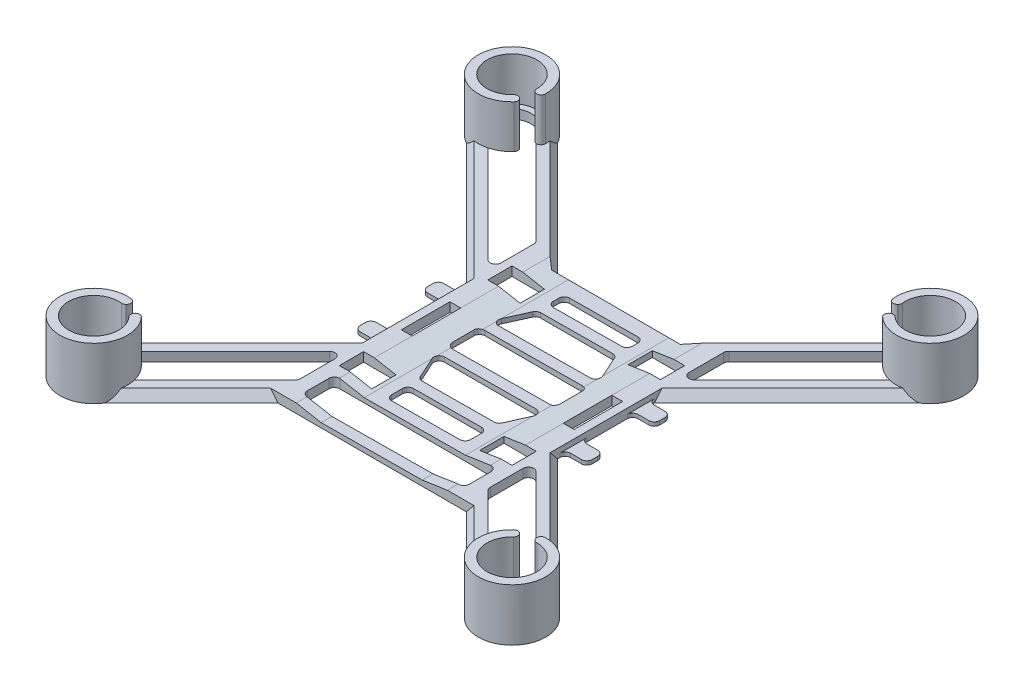
SolidWorks part; units mm, degrees
ref_plane "Plano frontal" through (0, 0, 0) normal (0, 0, 1) x (1, 0, 0)
ref_plane "Plano superior" through (0, 0, 0) normal (0, 1, 0) x (1, 0, 0)
ref_plane "Plano direito" through (0, 0, 0) normal (1, 0, 0) x (0, 0, -1)
sketch "Esboço1" plane through (0, 0, 0) normal (0, 1, 0) x (1, 0, 0)
  line L1 (-45, 45) -> (45, 45)
  line L2 (-45, 45) -> (-45, -45)
  line L3 (-45, -45) -> (45, -45)
  line L4 (45, 45) -> (45, -45)
  line L5 (-45, 45) -> (45, -45) construction
  line L6 (-45, -45) -> (45, 45) construction
  point P0 (0, 0)
  dimension "D1" = 90
  dimension "D2" = 90
extrude "Ressalto-extrusão1" add sketch "Esboço1" along normal blind 1.7
sketch "Esboço2" plane through (0, 1.7, 0) normal (0, 1, 0) x (1, 0, 0)
  line L0 (-45, 45) -> (-45, -45) construction
  line L1 (45, 45) -> (-45, 45) construction
  line L3 (45, -45) -> (45, 45) construction
  line L4 (-45, -45) -> (45, -45) construction
  circle A0 centre (-38.75, 38.75) radius 4.625
  circle A1 centre (38.75, 38.75) radius 4.625
  circle A2 centre (-38.75, -38.75) radius 4.625
  circle A3 centre (38.75, -38.75) radius 4.625
  circle A4 centre (-38.75, 38.75) radius 6.25
  circle A5 centre (38.75, 38.75) radius 6.25
  circle A6 centre (38.75, -38.75) radius 6.25
  circle A7 centre (-38.75, -38.75) radius 6.25
  dimension "D1" = 9.25
  dimension "D2" = 9.25
  dimension "D3" = 9.25
  dimension "D4" = 9.25
  dimension "D5" = 12.5
  dimension "D6" = 12.5
  dimension "D7" = 12.5
  dimension "D8" = 12.5
extrude "Ressalto-extrusão2" add sketch "Esboço2" along normal blind 8
fillet "Filete1" radius 6.25 4 edges at (-45, 0.85, -45) (45, 0.85, -45) (45, 0.85, 45) (-45, 0.85, 45)
sketch "Esboço3" plane through (0, 1.7, 0) normal (0, 1, 0) x (1, 0, 0)
  line L0 (0.3066, 3.9483) -> (37.2235, 40.8652)
  line L1 (40.8775, -36.6225) -> (39.4633, -38.0367)
  line L2 (-40.7706, -37.1289) -> (-39.3564, -38.5431)
  line L3 (-40.7706, -37.1289) -> (-1.1076, 2.5341)
  line L4 (37.2235, 40.8652) -> (38.6377, 39.451)
  line L5 (38.6377, 39.451) -> (1.7208, 2.5341)
  line L7 (40.8775, -36.6225) -> (1.7208, 2.5341)
  line L8 (-36.3856, 40.6405) -> (-37.7998, 39.2263)
  line L9 (-37.7998, 39.2263) -> (-1.1076, 2.5341)
  line L11 (0.3066, 3.9483) -> (-36.3856, 40.6405)
  line L12 (0.3066, 1.1199) -> (-39.3564, -38.5431)
  line L13 (0.3066, 1.1199) -> (39.4633, -38.0367)
  dimension "D1" = 2
  dimension "D3" = 2
extrude "Corte-extrusão1" cut sketch "Esboço3" along normal blind 15
sketch "Esboço11" plane through (0, 1.7, 0) normal (0, 1, 0) x (1, 0, 0)
  line L1 (-16, -16) -> (-10, -16)
  line L2 (-16, -16) -> (-16, -11.5)
  line L3 (-16, -11.5) -> (-10, -11.5)
  line L4 (-10, -16) -> (-10, -11.5)
  line L5 (-16, -4.5) -> (-14, -4.5)
  line L6 (-16, -4.5) -> (-16, 4.5)
  line L7 (-16, 4.5) -> (-14, 4.5)
  line L8 (-14, -4.5) -> (-14, 4.5)
  line L9 (-16, 11.5) -> (-10, 11.5)
  line L10 (-16, 11.5) -> (-16, 16)
  line L11 (-16, 16) -> (-10, 16)
  line L12 (-10, 11.5) -> (-10, 16)
  line L13 (10, -16) -> (16, -16)
  line L14 (10, -16) -> (10, -11.5)
  line L15 (10, -11.5) -> (16, -11.5)
  line L16 (16, -16) -> (16, -11.5)
  line L17 (16, -4.5) -> (14, -4.5)
  line L18 (16, -4.5) -> (16, 4.5)
  line L19 (16, 4.5) -> (14, 4.5)
  line L20 (14, -4.5) -> (14, 4.5)
  line L21 (16, 11.5) -> (10, 11.5)
  line L22 (16, 11.5) -> (16, 16)
  line L23 (16, 16) -> (10, 16)
  line L24 (10, 11.5) -> (10, 16)
  point P24 (-14, 0)
  dimension "D1" = 6
  dimension "D2" = 6
  dimension "D3" = 28
  dimension "D4" = 2
  dimension "D5" = 2
  dimension "D6" = 9
  dimension "D7" = 7
  dimension "D8" = 7
  dimension "D9" = 4.5
  dimension "D10" = 4.5
  dimension "D11" = 14
  dimension "D12" = 14
extrude "Corte-extrusão8" cut sketch "Esboço11" against normal blind 20
sketch "Esboço14" plane through (0, 1.7, 0) normal (0, 1, 0) x (1, 0, 0)
  line L2 (-34.3319, -43.1681) -> (-17.1431, -25.9793)
  line L3 (-44.9981, -38.75) -> (-47.943, -38.75)
  line L4 (-47.943, -38.75) -> (-47.943, 38.75)
  line L5 (-43.1681, -34.3319) -> (-17.5, -8.6638)
  line L6 (-34.3319, -43.1681) -> (-33.4507, -42.0602) construction
  line L7 (43.1681, 34.3319) -> (42.0602, 33.4507) construction
  line L8 (34.4073, -43.0927) -> (17.2939, -25.9793)
  line L9 (-47.943, 38.75) -> (-44.8915, 38.75)
  line L10 (-38.75, 44.8915) -> (-38.75, 46.9757)
  line L11 (43.0927, -34.4073) -> (17.5, -8.8146)
  line L12 (34.4073, -43.0927) -> (33.5537, -42.0237) construction
  line L13 (-43.0927, 34.4073) -> (-42.0237, 33.5537) construction
  line L15 (-38.75, 46.9757) -> (38.75, 46.9757)
  line L16 (-12.3146, 21) -> (12.1638, 21)
  line L17 (17.5, 8.6638) -> (17.5, -8.8146)
  line L18 (38.75, 46.9757) -> (38.75, 44.9981)
  line L22 (-17.5, 8.8146) -> (-43.0927, 34.4073)
  line L23 (17.5, 8.6638) -> (43.1681, 34.3319)
  line L24 (42.0237, -33.5537) -> (43.0927, -34.4073) construction
  line L25 (-33.5537, 42.0237) -> (-34.4073, 43.0927) construction
  line L26 (-12.3146, 21) -> (-34.4073, 43.0927)
  line L27 (12.1638, 21) -> (34.3319, 43.1681)
  line L28 (-17.5, 8.8146) -> (-17.5, -8.6638)
  line L29 (-17.1431, -25.9793) -> (17.2939, -25.9793)
  line L30 (44.9981, 38.75) -> (47.7164, 38.75)
  line L31 (47.7164, 38.75) -> (47.7164, -38.75)
  line L32 (47.7164, -38.75) -> (44.8915, -38.75)
  line L33 (-38.75, -44.9981) -> (-38.75, -47.5867)
  line L34 (-38.75, -47.5867) -> (38.75, -47.5867)
  line L35 (38.75, -47.5867) -> (38.75, -44.8915)
  line L36 (33.4507, 42.0602) -> (34.3319, 43.1681) construction
  line L37 (-42.0602, -33.4507) -> (-43.1681, -34.3319) construction
  arc A0 (-33.5537, 42.0237) -> (-38.75, 44.8915) centre (-38.75, 38.75) ccw
  arc A1 (42.0602, 33.4507) -> (44.9981, 38.75) centre (38.75, 38.75) ccw
  arc A2 (33.5537, -42.0237) -> (38.75, -44.8915) centre (38.75, -38.75) ccw
  arc A3 (-42.0602, -33.4507) -> (-44.9981, -38.75) centre (-38.75, -38.75) ccw
  arc A4 (-38.75, -44.9981) -> (-33.4507, -42.0602) centre (-38.75, -38.75) ccw
  arc A5 (44.8915, -38.75) -> (42.0237, -33.5537) centre (38.75, -38.75) ccw
  arc A6 (-44.8915, 38.75) -> (-42.0237, 33.5537) centre (-38.75, 38.75) ccw
  arc A7 (38.75, 44.9981) -> (33.4507, 42.0602) centre (38.75, 38.75) ccw
  point P8 (0, 0)
  point P9 (0, 0)
  point P10 (0, 0)
  arc M28 (37.0038, -32.7489) -> (45, -38.75) centre (38.75, -38.75) cw
  line M29 (45, -38.75) -> (45, 38.75)
  arc M30 (45, 38.75) -> (33.9427, 34.756) centre (38.75, 38.75) cw
  arc M34 (32.9023, 36.544) -> (38.75, 45) centre (38.75, 38.75) cw
  line M35 (38.75, 45) -> (-38.75, 45)
  arc M36 (-38.75, 45) -> (-32.7489, 37.0038) centre (-38.75, 38.75) cw
  arc M40 (-33.6753, 35.1018) -> (-45, 38.75) centre (-38.75, 38.75) cw
  line M41 (-45, 38.75) -> (-45, -38.75)
  arc M42 (-45, -38.75) -> (-36.544, -32.9023) centre (-38.75, -38.75) cw
  arc M46 (-34.756, -33.9427) -> (-38.75, -45) centre (-38.75, -38.75) cw
  line M47 (-38.75, -45) -> (38.75, -45)
  arc M48 (38.75, -45) -> (35.1018, -33.6753) centre (38.75, -38.75) cw
extrude "Corte-extrusão11" cut sketch "Esboço14" against normal blind 23 contours L28 L22 L5 M40 M41 M42 | L16 L27 L26 M34 M35 M36 | L23 L17 L11 M28 M29 M30 | L29 L2 L8 M46 M47 M48
sketch "Esboço17" plane through (0, 1.7, 0) normal (0, 1, 0) x (1, 0, 0)
  line L0 (17.5, 8.6638) -> (17.5, -8.8146) construction
  line L1 (-12.3146, 21) -> (-33.5874, 42.2728) construction
  line L2 (-40.125, -35.5314) -> (-17.5, -12.9064)
  line L3 (-17.5, 13.0572) -> (-17.5, 21.9428)
  line L4 (-17.5, 8.8146) -> (-17.5, -8.6638) construction
  line L5 (-35.5314, -40.125) -> (-17.5, -22.0936)
  line L7 (17.5, 8.6638) -> (43.0606, 34.2244) construction
  line L8 (-39.8803, 35.4375) -> (-17.5, 13.0572)
  line L9 (-17.5, 8.8146) -> (-42.2728, 33.5874) construction
  line L10 (-43.0606, -34.2244) -> (-17.5, -8.6638) construction
  line L11 (-35.4375, 39.8803) -> (-17.5, 21.9428)
  line L12 (12.1638, 21) -> (34.2244, 43.0606) construction
  line L14 (17.5, -21.9428) -> (17.5, -13.0572)
  line L15 (42.2728, -33.5874) -> (17.5, -8.8146) construction
  line L17 (-17.5, -22.0936) -> (-17.5, -12.9064)
  line L21 (17.5, 12.9064) -> (40.125, 35.5314)
  line L27 (17.5, -21.9428) -> (35.4375, -39.8803)
  line L31 (17.5, -13.0572) -> (39.8803, -35.4375)
  line L35 (17.5, 22.0936) -> (35.5314, 40.125)
  line L37 (17.5, 12.9064) -> (17.5, 22.0936)
  arc A0 (-35.4375, 39.8803) -> (-39.8803, 35.4375) centre (-38.75, 38.75) ccw
  circle A1 centre (-38.75, 38.75) radius 4.625 construction
  arc A2 (40.125, 35.5314) -> (35.5314, 40.125) centre (38.75, 38.75) ccw
  arc A3 (-40.125, -35.5314) -> (-35.5314, -40.125) centre (-38.75, -38.75) ccw
  arc A4 (35.4375, -39.8803) -> (39.8803, -35.4375) centre (38.75, -38.75) ccw
  circle A5 centre (-38.75, -38.75) radius 4.625 construction
  circle A6 centre (38.75, -38.75) radius 4.625 construction
  circle A7 centre (38.75, 38.75) radius 4.625 construction
  point P9 (0, 0)
  point P10 (-0.8277, 0.587)
  point P11 (0, 0)
  dimension "D3" = 7
  dimension "D6" = 7
  dimension "D4" = 7
  dimension "D7" = 7
  dimension "D2" = 3
  dimension "D5" = 3
  dimension "D8" = 3
  dimension "D9" = 3
  dimension "D10" = 3
  dimension "D11" = 3
  dimension "D12" = 3
chamfer "Chanfro2" distance 2 angle 30 16 edges at (29.8864, 0, 21.201) (29.8864, 1.7, 21.201) (-30.2803, 1.7, 21.4441) (-30.2803, 0, 21.4441) (-22.951, 0, -31.6364) (-22.951, 1.7, -31.6364) (23.1941, 1.7, -32.0303) (23.1941, 0, -32.0303) (-29.8864, 1.7, -21.201) (-29.8864, 0, -21.201) (30.2803, 0, -21.4441) (30.2803, 1.7, -21.4441) (25.4407, 1.7, 34.1261) (25.4407, 0, 34.1261) (-25.6837, 0, 34.5199) (-25.6837, 1.7, 34.5199)
sketch "Esboço23" plane through (0, 1.7, 0) normal (0, 1, 0) x (1, 0, 0)
  line L1 (-17.5, 4.8565) -> (-21.5, 4.8565)
  line L2 (-17.5, 4.8565) -> (-17.5, 7.8565)
  line L3 (-17.5, 7.8565) -> (-21.5, 7.8565)
  line L4 (-21.5, 4.8565) -> (-21.5, 7.8565)
  line L5 (17.5, 10.2968) -> (17.5, -10.4476) construction
  line L6 (17.5, 4.8565) -> (21.5, 4.8565)
  line L7 (17.5, 4.8565) -> (17.5, 7.8565)
  line L8 (17.5, 7.8565) -> (21.5, 7.8565)
  line L9 (21.5, 4.8565) -> (21.5, 7.8565)
  line L10 (-17.5, 10.4476) -> (-17.5, -10.2968) construction
  line L11 (-17.5, -7.6321) -> (-21.5, -7.6321)
  line L12 (-17.5, -7.6321) -> (-17.5, -4.6321)
  line L13 (-17.5, -4.6321) -> (-21.5, -4.6321)
  line L14 (-21.5, -7.6321) -> (-21.5, -4.6321)
  line L16 (17.5, -7.6321) -> (21.5, -7.6321)
  line L17 (17.5, -7.6321) -> (17.5, -4.6321)
  line L18 (17.5, -4.6321) -> (21.5, -4.6321)
  line L19 (21.5, -7.6321) -> (21.5, -4.6321)
  dimension "D1" = 4
  dimension "D2" = 4
  dimension "D3" = 3
  dimension "D4" = 3
  dimension "D5" = 4
  dimension "D6" = 4
extrude "Ressalto-extrusão6" add sketch "Esboço23" against normal blind 1.7
sketch "Esboço25" plane through (0, 1.7, 0) normal (0, 1, 0) x (1, 0, 0)
  line L0 (-18.7761, -25.9793) -> (18.9269, -25.9793) construction
  line L1 (-14.9246, -17.9793) -> (15.0754, -17.9793)
  line L2 (-14.9246, -17.9793) -> (-14.9246, -23.9793)
  line L3 (-14.9246, -23.9793) -> (15.0754, -23.9793)
  line L4 (15.0754, -17.9793) -> (15.0754, -23.9793)
  line L5 (-14.9246, -17.9793) -> (15.0754, -23.9793) construction
  line L6 (-14.9246, -23.9793) -> (15.0754, -17.9793) construction
  line L7 (-7.316, -11.9793) -> (7.316, -11.9793)
  line L8 (-7.316, -11.9793) -> (-7.316, -15.9793)
  line L9 (-7.316, -15.9793) -> (7.316, -15.9793)
  line L10 (7.316, -11.9793) -> (7.316, -15.9793)
  line L11 (-7.316, -11.9793) -> (7.316, -15.9793) construction
  line L12 (-7.316, -15.9793) -> (7.316, -11.9793) construction
  line L13 (-10.033, -4.0138) -> (10, -4.0138)
  line L14 (-10.033, -4.0138) -> (-7.316, -9.9793)
  line L15 (-7.316, -9.9793) -> (7.316, -9.9793)
  line L16 (10, -4.0138) -> (7.316, -9.9793)
  line L17 (-18.7761, -25.9793) -> (18.9269, -25.9793) construction
  line L19 (-10, 3.9862) -> (10, 3.9862)
  line L20 (-10, 3.9862) -> (-10, -2.0138)
  line L21 (-10, -2.0138) -> (10, -2.0138)
  line L22 (10, 3.9862) -> (10, -2.0138)
  line L23 (-10, 3.9862) -> (10, -2.0138) construction
  line L24 (-10, -2.0138) -> (10, 3.9862) construction
  line L25 (-7.316, 11.977) -> (7.316, 11.977)
  line L26 (-7.316, 11.977) -> (-10.0155, 5.9862)
  line L27 (-10.0155, 5.9862) -> (10.0155, 5.9862)
  line L28 (7.316, 11.977) -> (10.0155, 5.9862)
  line L31 (-7.316, 17) -> (7.316, 17)
  line L32 (-7.316, 17) -> (-7.316, 13.977)
  line L33 (-7.316, 13.977) -> (7.316, 13.977)
  line L34 (7.316, 17) -> (7.316, 13.977)
  line L35 (-7.316, 17) -> (7.316, 13.977) construction
  line L36 (-7.316, 13.977) -> (7.316, 17) construction
  line L37 (-13.9476, 21) -> (13.7968, 21) construction
  point P0 (0.0754, -20.9793)
  point P5 (0, -13.9793)
  point P10 (0, -6.9793)
  point P15 (0, 0.9862)
  point P20 (0, 9.0207)
  point P25 (0, 15.4885)
  point P36 (0.0754, -25.9793)
  dimension "D1" = 6
  dimension "D2" = 2
  dimension "D3" = 2
  dimension "D4" = 2
  dimension "D5" = 2
  dimension "D6" = 2
  dimension "D7" = 2
  dimension "D8" = 4
  dimension "D9" = 4
  dimension "D10" = 30
  dimension "D11" = 6
  dimension "D12" = 5
  dimension "D13" = 20
extrude "Corte-extrusão16" cut sketch "Esboço25" against normal blind 34
chamfer "Chanfro4" distance 2 angle 45 2 edges at (-0.0754, 0, -21) (-0.0754, 1.7, -21)
extrude "Corte-extrusão20" cut sketch "Esboço17" against normal blind 4
fillet "Filete5" radius 1 24 edges at (7.316, 0.85, -13.977) (10.0155, 0.85, -5.9862) (10, 0.85, 2.0138) (7.316, 0.85, 9.9793) (7.316, 0.85, 15.9793) (15.0754, 0.85, 23.9793) (7.316, 0.85, -11.977) (10, 0.85, -3.9862) (10, 0.85, 4.0138) (7.316, 0.85, 11.9793) (15.0754, 0.85, 17.9793) (7.316, 0.85, -17) (-10.0155, 0.85, -5.9862) (-10.033, 0.85, 4.0138) (-7.316, 0.85, -17) (-7.316, 0.85, -11.977) (-10, 0.85, -3.9862) (-7.316, 0.85, 11.9793) (-14.9246, 0.85, 17.9793) (-7.316, 0.85, -13.977) (-10, 0.85, 2.0138) (-7.316, 0.85, 9.9793) (-7.316, 0.85, 15.9793) (-14.9246, 0.85, 23.9793)
fillet "Filete6" radius 1 16 edges at (17.5, 0.85, -22.0936) (-17.5, 0.85, -13.0572) (17.5, 0.85, -7.8565) (17.5, 0.85, 4.6321) (17.5, 0.85, -4.8565) (17.5, 0.85, 7.6321) (-17.5, 0.85, 7.6321) (17.5, 0.85, 13.0572) (-17.5, 0.85, 12.9064) (-17.5, 0.85, 4.6321) (-17.5, 0.85, -4.8565) (-17.5, 0.85, -7.8565) (-17.5, 0.85, -21.9428) (-17.5, 0.85, 22.0936) (17.5, 0.85, 21.9428) (17.5, 0.85, -12.9064)
fillet "Filete7" radius 1 8 edges at (21.5, 0.85, -7.8565) (21.5, 0.85, -4.8565) (21.5, 0.85, 4.6321) (21.5, 0.85, 7.6321) (-21.5, 0.85, 7.6321) (-21.5, 0.85, 4.6321) (-21.5, 0.85, -4.8565) (-21.5, 0.85, -7.8565)
sketch "Esboço26" plane through (0, 0, 25.9793) normal (0, 0, 1) x (1, 0, 0)
  line L1 (-14, 1.7) -> (14, 1.7)
  line L2 (-14, 1.7) -> (-9.3888, 0.85)
  line L3 (-9.3888, 0.85) -> (9.3655, 1)
  line L4 (14, 1.7) -> (9.3655, 1)
  line L7 (-9.3888, 0) -> (-9.3888, 1.7) construction
  point P4 (-9.3888, 2)
  point P5 (-12.5, 2)
  point P6 (-11.9267, 1.1807)
  point P7 (-10.5103, 1)
  point P8 (-9.3888, 1)
  point P13 (12.5, 2)
extrude "Corte-extrusão21" cut sketch "Esboço26" against normal through all
sketch "Esboço30" plane through (0, 1.7, 0) normal (0, 1, 0) x (1, 0, 0)
  line L0 (-17.5, 8.8565) -> (-17.5, -8.7432)
  line L1 (-17.5, 8.8565) -> (-22.1246, 8.8565)
  line L2 (-17.5, -8.7432) -> (-22.1246, -8.7432)
  line L3 (-22.1246, 8.8565) -> (-22.1246, -8.7432)
  line L4 (17.5, 8.8565) -> (17.5, -9.0596)
  line L5 (17.5, 8.8565) -> (22.2206, 8.8565)
  line L6 (17.5, -9.0596) -> (22.2206, -9.0596)
  line L7 (22.2206, 8.8565) -> (22.2206, -9.0596)
  line L8 (-17.5, -8.6321) -> (-17.5, -10.2968) construction
  point P0 (17.5, 8.8565)
extrude "Corte-extrusão25" cut sketch "Esboço30" against normal blind 1
fillet "Filete8" radius 0.8 16 edges at (-33.6753, 5.7, -35.1018) (-34.8451, 5.7, -36.2716) (32.9023, 5.7, -36.544) (34.2126, 5.7, -37.8543) (36.2716, 5.7, 34.8451) (35.1018, 5.7, 33.6753) (-34.756, 5.7, 33.9427) (-35.9117, 5.7, 35.0984) (-32.7489, 5.7, -37.0038) (-34.1387, 5.7, -38.3937) (33.9427, 5.7, -34.756) (35.0984, 5.7, -35.9117) (38.3937, 5.7, 34.1387) (37.0038, 5.7, 32.7489) (-36.544, 5.7, 32.9023) (-37.8543, 5.7, 34.2126)
